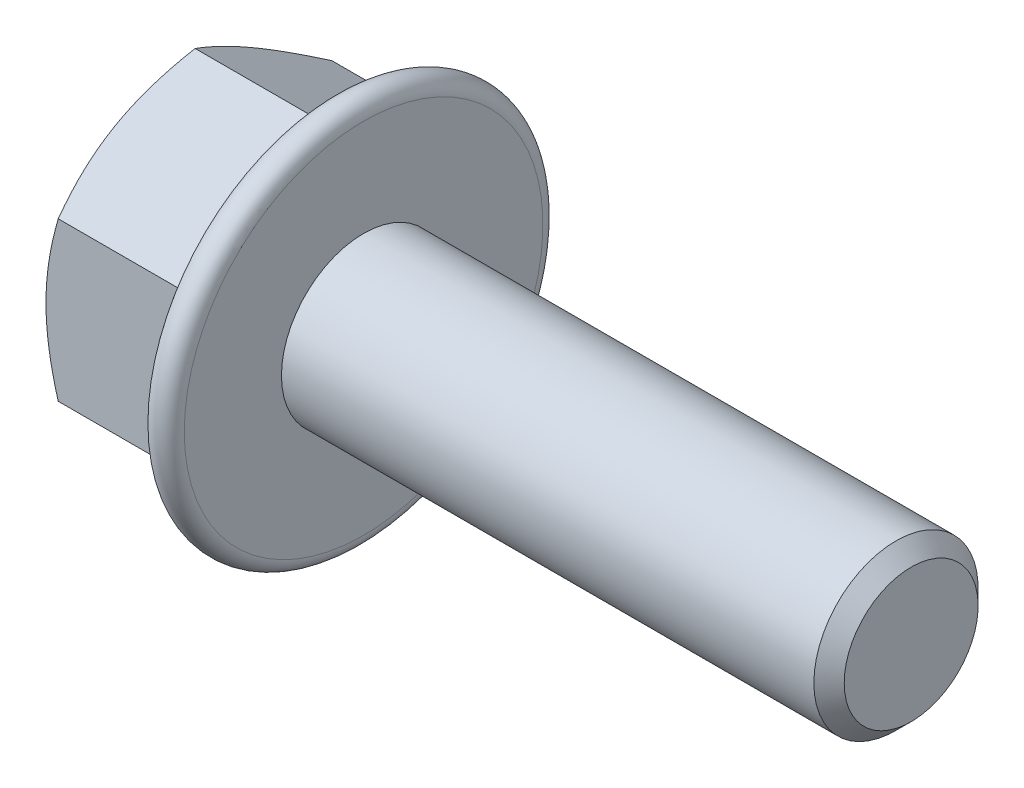
SolidWorks part; units mm, degrees
ref_plane "Plane1" through (0, 0, 0) normal (0, 0, 1) x (1, 0, 0)
ref_plane "Plane2" through (0, 0, 0) normal (0, 1, 0) x (1, 0, 0)
ref_plane "Plane3" through (0, 0, 0) normal (1, 0, 0) x (0, 0, -1)
sketch "Sketch1" plane through (0, 0, 0) normal (1, 0, 0) x (0, 0, -1)
  line L0 (5, 2.8868) -> (5, -2.8868)
  line L1 (-5, 2.8868) -> (-5, -2.8868)
  line L2 (5, -2.8868) -> (0, -5.7735)
  line L3 (0, -5.7735) -> (-5, -2.8868)
  line L4 (5, 2.8868) -> (0, 5.7735)
  line L5 (0, 5.7735) -> (-5, 2.8868)
  dimension "Width_flats" = 10
  dimension "D2" = 120
  dimension "D3" = 5
  dimension "D4" = 5
  dimension "D5" = 5
extrude "BaseHead" add sketch "Sketch1" along normal blind 6.6
sketch "BodySke" plane through (0, 0, 0) normal (0, 0, 1) x (1, 0, 0)
  line L0 (0, 2.8868) -> (0, -2.8868) construction
  line L1 (0, 0) -> (26.6, 0)
  line L2 (0, 0) -> (0, 3)
  line L3 (0, 3) -> (26.0455, 3)
  line L4 (26.6, 0) -> (26.6, 2.4455)
  line L5 (6.6, 5.7735) -> (6.6, 2.8868) construction
  line L6 (26.6, 2.4455) -> (26.0455, 3)
  line L7 (0, 0) -> (96.52, 0) construction
  line L8 (26.6, -2.4455) -> (26.0455, -3) construction
  line L9 (0, -3) -> (26.0455, -3) construction
  line L10 (7.6, 15.24) -> (7.6, -1.27) construction
  line L11 (6.6, 15.24) -> (6.6, -1.27) construction
  line L12 (6.6, 2.8868) -> (6.6, -2.8868) construction
  dimension "Length" = 20
  dimension "Body_ch_ang" = 45
  dimension "Diameter" = 6
  dimension "Minor_dia" = 4.891
  dimension "Advance" = 1
  dimension "Thread_nom" = 20
revolve "BaseBody" add sketch "BodySke"
cosmetic thread "ThreadCosmetic" [suppressed]
fillet "HeadFillet" [suppressed] radius 0.25
sketch "Sketch3" plane through (0, 0, 0) normal (0, 0, 1) x (1, 0, 0)
  line L0 (0, 5) -> (3.3333, 10.7735)
  line L1 (0, 5.7735) -> (0, 2.8868) construction
  line L2 (3.3333, 10.7735) -> (3.3333, 15.7735)
  line L3 (3.3333, 15.7735) -> (-10, 15.7735)
  line L4 (-10, 15.7735) -> (-10, 5)
  line L5 (-10, 5) -> (0, 5)
  line L6 (0, 0) -> (99.06, 0) construction
  line L7 (6.6, 5.7735) -> (0, 5.7735) construction
  dimension "D1" = 5
  dimension "D2" = 5
  dimension "D3" = 10
  dimension "D4" = 5
  dimension "Head_ch_ang" = 30
revolve "HeadChamfer" cut sketch "Sketch3" angle 360 about L6
sketch "Sketch4" plane through (0, 0, 0) normal (0, 0, 1) x (1, 0, 0)
  line L0 (3.0807, 0) -> (5.5332, 6.7381)
  line L1 (6.6, 5.7735) -> (6.6, 2.8868) construction
  line L2 (5.5, 34.3444) -> (5.5, 16.9779) construction
  line L3 (6.6, 0) -> (6.6, 6.55)
  line L4 (8.3021, 7.1) -> (20.1618, 7.1) construction
  line L5 (0, 0) -> (95.25, 0) construction
  line L6 (0, 0) -> (96.52, 0) construction
  line L7 (3.0807, 0) -> (6.6, 0)
  line L8 (8.3021, -7.1) -> (20.1618, -7.1) construction
  arc A0 (6.6, 6.55) -> (5.5332, 6.7381) centre (6.05, 6.55) ccw
  dimension "D1" = 20
  dimension "Flange_thickness" = 1.1
  dimension "Flange_dia" = 14.2
revolve "Flange" add sketch "Sketch4" angle 360 about L5
fillet "FlangeHexFillet" radius 0.4 6 edges
sketch "ThdSchSke" plane through (0, 0, 0) normal (0, 0, 1) x (1, 0, 0)
  line L0 (7.6, -2.4455) -> (7.2117, -3)
  line L1 (7.6, -2.4455) -> (7.9883, -3)
  line L2 (7.9883, -3) -> (7.9883, -3.75)
  line L3 (-3.175, 0) -> (5.1513, 0) construction
  line L5 (7.9883, -3.75) -> (7.2117, -3.75)
  line L6 (7.2117, -3.75) -> (7.2117, -3)
  dimension "Thread_minor" = 4.891
  dimension "Diameter" = 6
  dimension "Start" = 7.6
  dimension "SideAngle" = 55
  dimension "VeeAngle" = 70
  dimension "Overcut" = 7.5
revolve "ThreadSchematic" [suppressed] cut sketch "ThdSchSke" angle 360 about L3
pattern_linear "ThdSchPat" [suppressed]
equation "\"D3@Sketch1\" = \"Width_flats@Sketch1\" / 2"
equation "\"D4@Sketch1\" = \"D3@Sketch1\""
equation "\"D5@Sketch1\" = \"D4@Sketch1\""
equation "\"Thread_minor@ThreadCosmetic\" = \"Minor_dia@BodySke\""
equation "\"D1@Sketch3\" = \"Width_flats@Sketch1\" / 2"
equation "\"Thread_length@ThreadCosmetic\" = ((sgn( (\"Length@BodySke\" - \"Advance@BodySke\" ) - \"Thread_nom@BodySke\" )-1)*( (\"Length@BodySke\" - \"Advance@BodySke\" ) - \"Thread_nom@BodySke\" ))/-2+ \"Thread_nom@BodySke\""
equation "\"Thread_minor@ThdSchSke\" = \"Minor_dia@BodySke\""
equation "\"Diameter@ThdSchSke\" = \"Diameter@BodySke\""
equation "\"Overcut@ThdSchSke\" = \"Diameter@BodySke\" * 1.25"
equation "\"Start@ThdSchSke\" = \"Head_ht@BaseHead\" + \"Length@BodySke\" - \"Thread_length@ThreadCosmetic\"  '---Non-countersunk---"
equation "\"Num_threads@ThdSchPat\" = int( \"Thread_length@ThreadCosmetic\" / \"Advance@BodySke\" + 0.999 )  + 1"
equation "\"Advance@ThdSchPat\" = \"Thread_length@ThreadCosmetic\" /  (\"Num_threads@ThdSchPat\" - 1) 'relax it"
equation "\"Num_threads@ThdSchPat\" = \"Num_threads@ThdSchPat\" - sgn( \"Num_threads@ThdSchPat\" - 1) '---chamfered tips only---"
